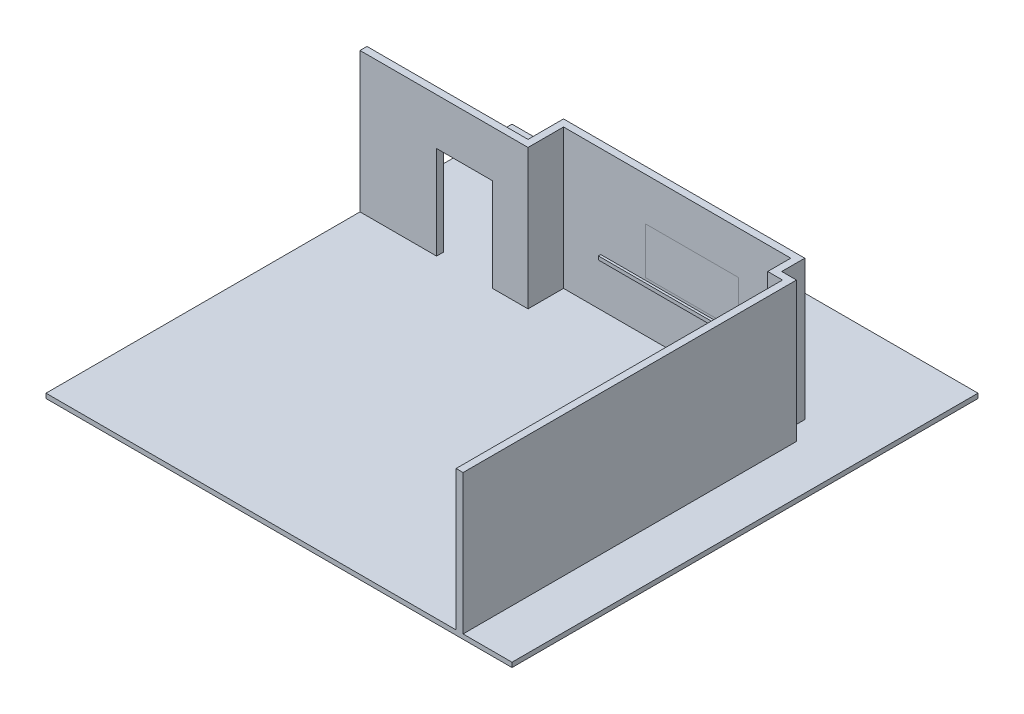
SolidWorks part; units mm, degrees
other "power_strip"
other "Cabinet"
other "window"
material "Concrete"
ref_plane "Front Plane" through (0, 0, 0) normal (0, 0, 1) x (1, 0, 0)
ref_plane "Top Plane" through (0, 0, 0) normal (0, 1, 0) x (1, 0, 0)
ref_plane "Right Plane" through (0, 0, 0) normal (1, 0, 0) x (0, 0, -1)
sketch "Sketch1" plane through (0, 0, 0) normal (0, 1, 0) x (1, 0, 0)
  line L1 (-5000, -5000) -> (5000, -5000)
  line L2 (-5000, -5000) -> (-5000, 5000)
  line L3 (-5000, 5000) -> (5000, 5000)
  line L4 (5000, -5000) -> (5000, 5000)
  line L5 (0, 5000) -> (0, -5000) construction
  line L6 (-5000, 0) -> (5000, 0) construction
  point P0 (0, 0)
  dimension "D1" = 10000
  dimension "D2" = 10000
extrude "Boss-Extrude1" add sketch "Sketch1" against normal blind 100
sketch "Sketch3" plane through (0, 0, 0) normal (0, 1, 0) x (1, 0, 0)
  line L0 (3482.5, 2500) -> (-1394.3, 2500)
  line L1 (-1394.3, 2500) -> (-1394.3, 1738)
  line L2 (-1394.3, 1738) -> (-5000, 1738)
  line L3 (-5000, 5000) -> (-5000, -5000) construction
  line L4 (3482.5, 2500) -> (3482.5, 2005)
  line L5 (3482.5, 2005) -> (3800, 2005)
  line L6 (3800, 2005) -> (3800, -5000)
  line L7 (-5000, -5000) -> (5000, -5000) construction
  line L8 (3950, 2155) -> (3950, -5000)
  line L9 (3632.5, 2155) -> (3950, 2155)
  line L10 (3632.5, 2650) -> (3632.5, 2155)
  line L11 (3632.5, 2650) -> (-1544.3, 2650)
  line L12 (-1544.3, 2650) -> (-1544.3, 1888)
  line L13 (-1544.3, 1888) -> (-5000, 1888)
  line L14 (5000, -5000) -> (5000, 5000) construction
  line L15 (5000, 5000) -> (-5000, 5000) construction
  line L16 (-5000, 1888) -> (-5000, 1738)
  line L17 (3800, -5000) -> (3950, -5000)
  dimension "D2" = 1200
  dimension "D3" = 2500
  dimension "D4" = 495
  dimension "D5" = 317.5
  dimension "D6" = 762
  dimension "D7" = 4876.8
  dimension "D1" = 150
extrude "Boss-Extrude2" add sketch "Sketch3" along normal blind 3000
sketch "Sketch4" plane through (0, 0, -2500) normal (0, 0, 1) x (1, 0, 0)
  line L0 (-1394.3, 0) -> (3482.5, 0) construction
  line L1 (364.9, 1079.5) -> (2364.9, 1079.5)
  line L2 (364.9, 1079.5) -> (364.9, 2079.5)
  line L3 (364.9, 2079.5) -> (2364.9, 2079.5)
  line L4 (2364.9, 1079.5) -> (2364.9, 2079.5)
  line L5 (3482.5, 3000) -> (3482.5, 0) construction
  line L6 (-5000, 0) -> (3800, 0) construction
  line L7 (-3356.3, 0) -> (-2156.3, 0)
  line L8 (-3356.3, 0) -> (-3356.3, 2000)
  line L9 (-3356.3, 2000) -> (-2156.3, 2000)
  line L10 (-2156.3, 0) -> (-2156.3, 2000)
  line L11 (-1394.3, 3000) -> (-1394.3, 0) construction
  dimension "D1" = 1079.5
  dimension "D2" = 1117.6
  dimension "D3" = 2000
  dimension "D4" = 1000
  dimension "D5" = 762
  dimension "D6" = 1200
  dimension "D7" = 2000
sketch "Sketch5" plane through (0, 0, 0) normal (0, 1, 0) x (1, 0, 0)
  line L0 (3800, 2005) -> (3800, -5000) construction
  line L1 (3800, 887.4) -> (3241.2, 887.4)
  line L2 (3800, 887.4) -> (3800, -37.16)
  line L3 (3800, -37.16) -> (3241.2, -37.16)
  line L4 (3241.2, 887.4) -> (3241.2, -37.16)
  line L5 (3482.5, 2005) -> (3800, 2005) construction
  dimension "D1" = 558.8
  dimension "D2" = 924.56
  dimension "D3" = 1117.6
extrude "Cut-Extrude1" cut sketch "Sketch4" against normal through all both and the other way through all
extrude "Boss-Extrude3" add sketch "Sketch4<2>" against normal up to surface (150 mm away) from surface separate body contours L1 L4 L3 L2 region at (1364.9, 1579.5, -2500) up to face at (1364.9, 1579.5, -2650) starting at face at (1364.9, 1579.5, -2500)
sketch "Sketch4<2>" plane through (0, 0, -2500) normal (0, 0, 1) x (1, 0, 0) same geometry as "Sketch4"
extrude "Boss-Extrude4" add sketch "Sketch5" along normal blind 1900 separate body
sketch "Sketch6" plane through (0, 0, -2500) normal (0, 0, 1) x (1, 0, 0)
  line L1 (-594.3, 1028.7) -> (3482.5, 1028.7)
  line L2 (-594.3, 1028.7) -> (-594.3, 952.5)
  line L3 (-594.3, 952.5) -> (3482.5, 952.5)
  line L4 (3482.5, 1028.7) -> (3482.5, 952.5)
  line L5 (3482.5, 3000) -> (3482.5, 0) construction
  line L6 (2364.9, 1079.5) -> (364.9, 1079.5) construction
  line L7 (-1394.3, 3000) -> (-1394.3, 0) construction
  dimension "D1" = 76.2
  dimension "D2" = 50.8
  dimension "D3" = 800
extrude "Boss-Extrude5" add sketch "Sketch6" along normal blind 50.8 separate body
sketch "Sketch7" plane through (0, 0, 0) normal (0, 1, 0) x (1, 0, 0)
  line L0 (-1394.3, 2500) -> (3482.5, 2500) construction
  line L1 (1494.9417, 518.8) -> (294.9417, 518.8)
  line L2 (1494.9417, 518.8) -> (1494.9417, -3151.3213)
  line L3 (1494.9417, -3151.3213) -> (294.9417, -3151.3213)
  line L4 (294.9417, 518.8) -> (294.9417, -3151.3213)
  dimension "D1" = 1981.2
  dimension "D2" = 1200
extrude "Boss-Extrude6" [suppressed] add sketch "Sketch7" along normal blind 2438.4
